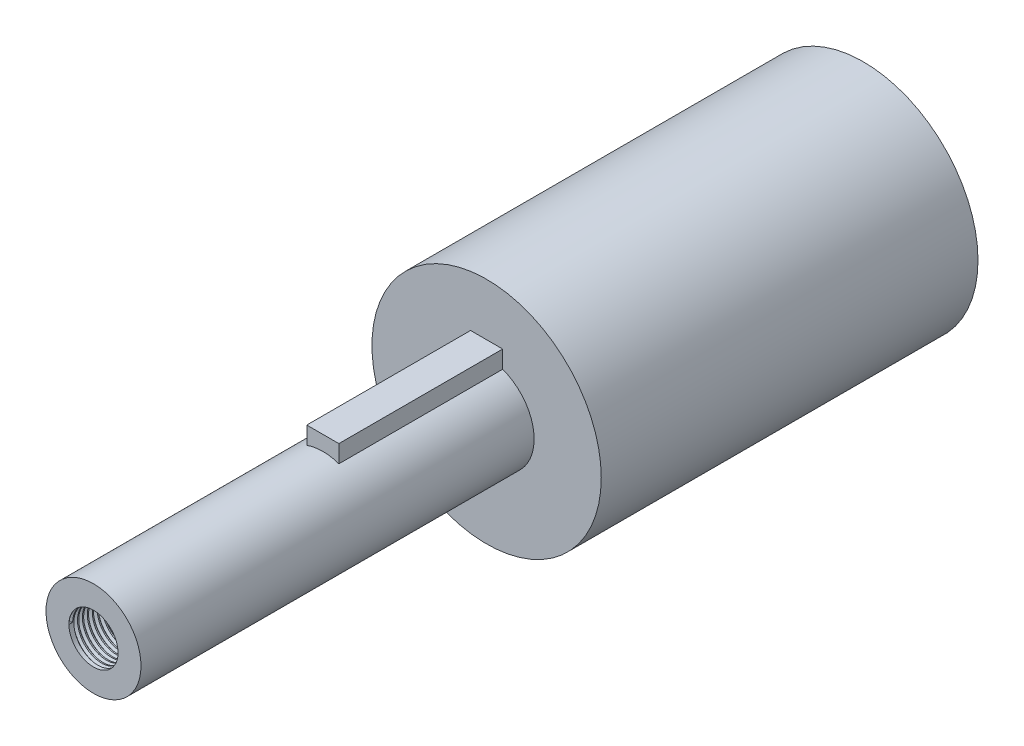
SolidWorks part; units mm, degrees
ref_plane "Front Plane" through (0, 0, 0) normal (1, 0, 0) x (0, 1, 0)
ref_plane "Top Plane" through (0, 0, 0) normal (0, 0, 1) x (0, 1, 0)
ref_plane "Right Plane" through (0, 0, 0) normal (0, 1, 0) x (-1, 0, 0)
sketch "Sketch1" plane through (0, 0, 0) normal (0, 0, 1) x (0, 1, 0)
  circle A0 centre (0, 0) radius 7
  dimension "D1" = 14
extrude "Boss-Extrude1" add sketch "Sketch1" along normal blind 23
sketch "Sketch2" plane through (0, 0, 23) normal (0, 0, 1) x (1, 0, 0)
  circle A0 centre (0, 0) radius 2.9
  dimension "D1" = 5.8
extrude "Boss-Extrude2" add sketch "Sketch2" along normal blind 24
sketch "Sketch5" plane through (0, 0, 0) normal (0, 0, -1) x (1, 0, 0)
  circle A0 centre (0, 0) radius 5.5
  dimension "D1" = 11
extrude "Cut-Extrude3" cut sketch "Sketch5" against normal blind 7
sketch "Sketch6" plane through (0, 0, 23) normal (0, 0, 1) x (1, 0, 0)
  line L0 (0.98, 2.8354) -> (0.98, 2.7294)
  line L1 (0, 3.8) -> (0.98, 3.8)
  line L2 (0, 3.8) -> (-0.98, 3.8)
  line L3 (-0.98, 3.8) -> (-0.98, 2.8354)
  line L4 (0.98, 3.8) -> (0.98, 2.8354)
  line L5 (-0.98, 2.8354) -> (-0.98, 2.7294)
  arc A1 (0.98, 2.7294) -> (-0.98, 2.7294) centre (0, 0) ccw
  dimension "D5" = 5.8
  dimension "D2" = 0.98
  dimension "D3" = 0.98
  dimension "D4" = 3.8
extrude "Boss-Extrude5" add sketch "Sketch6" along normal blind 10
sketch "Sketch7" plane through (0, 0, 7) normal (0, 0, -1) x (1, 0, 0)
  circle A0 centre (0, 0) radius 2.25
  dimension "D1" = 4.5
extrude "Cut-Extrude4" cut sketch "Sketch7" against normal blind 30
sketch "Sketch8" plane through (0, 0, 47) normal (0, 0, 1) x (1, 0, 0)
  circle A0 centre (0, 0) radius 1.5
  dimension "D1" = 3
extrude "Cut-Extrude5" cut sketch "Sketch8" against normal blind 20
thread "Thread1" pitch 0.3 method cut profile "Thread Profile1" start angle 0, offset 0.0001, length 6, pitch 0.3, diameter 3
ref_plane "Plane1" through (-1.5, 0, 46.9999) normal (0, -1, 0) x (-1, 0, 0)
sketch "Thread Profile1" plane through (-1.5, 0, 46.9999) normal (0, -1, 0) x (-1, 0, 0)
  line L0 (0, 0) -> (0, 0.3) construction
  line L1 (0, 0) -> (0.1624, 0.0937)
  line L2 (0.1624, 0.0937) -> (0.1624, 0.1312)
  line L3 (0.1624, 0.1312) -> (0, 0.225)
  line L4 (0.1624, 0.1125) -> (0, 0.1125) construction
  line L11 (0, 0) -> (0, 0.225)
  point P2 (0, 0)
  dimension "Pitch" = 0.3
  dimension "Profile_Angle" = 60
  dimension "Profile_Land" = 0.0375
  dimension "Profile_Height" = 0.1624
